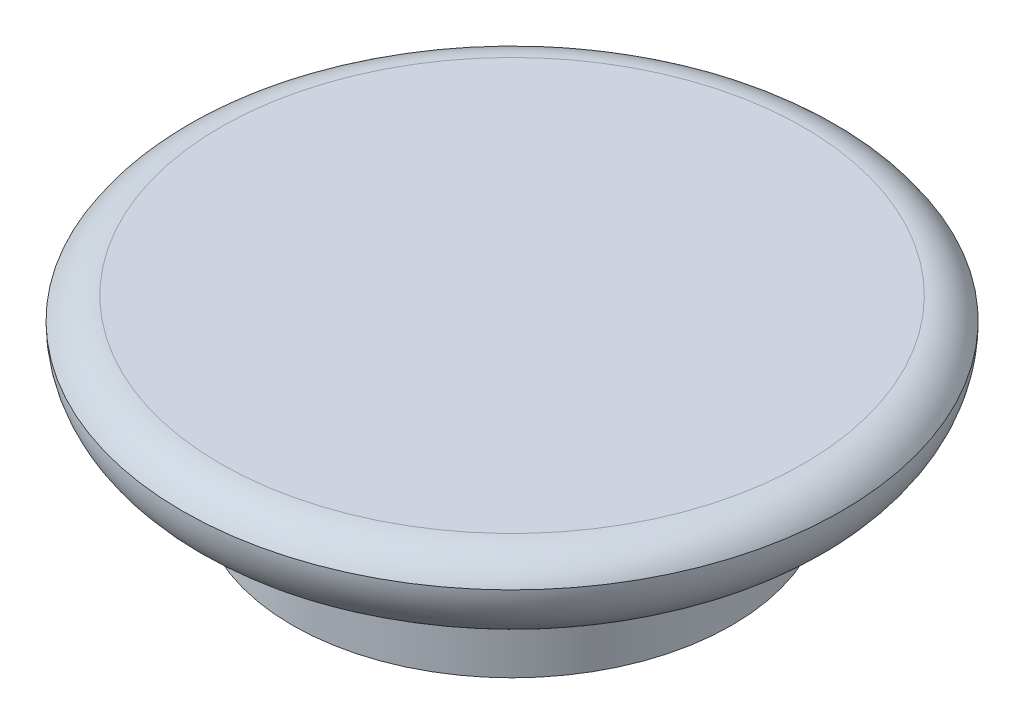
SolidWorks part; units mm, degrees
ref_plane "Front Plane" through (0, 0, 0) normal (0, 0, 1) x (1, 0, 0)
ref_plane "Top Plane" through (0, 0, 0) normal (0, 1, 0) x (1, 0, 0)
ref_plane "Right Plane" through (0, 0, 0) normal (1, 0, 0) x (0, 0, -1)
sketch "Sketch1" plane through (0, 0, 0) normal (0, 1, 0) x (1, 0, 0)
  circle A0 centre (0, 0) radius 50
  dimension "D1" = 100
extrude "Boss-Extrude1" add sketch "Sketch1" along normal blind 20
ref_plane "Plane1" through (0, 20, 0) normal (0, 1, 0) x (1, 0, 0)
sketch "Sketch2" plane through (0, 20, 0) normal (0, 1, 0) x (1, 0, 0)
  circle A1 centre (0, 0) radius 75
  point P4 (0, 0)
  dimension "D1" = 150
extrude "Boss-Extrude2" add sketch "Sketch2" along normal blind 20
fillet "Fillet1" radius 15 1 edges at (0, 20, 75)
fillet "Fillet3" radius 10 1 edges at (0, 40, 75)
